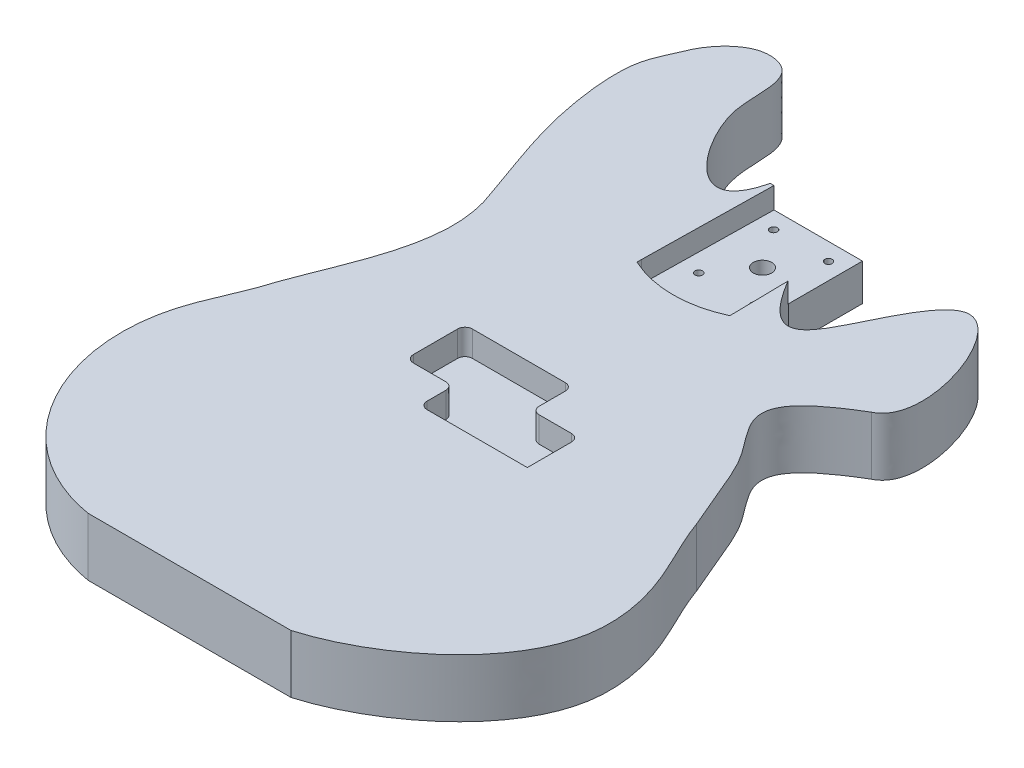
SolidWorks part; units mm, degrees
ref_plane "Front Plane" through (0, 0, 0) normal (0, 0, 1) x (1, 0, 0)
ref_plane "Top Plane" through (0, 0, 0) normal (0, 1, 0) x (1, 0, 0)
ref_plane "Right Plane" through (0, 0, 0) normal (1, 0, 0) x (0, 0, -1)
sketch "Sketch1" plane through (0, 0, 0) normal (0, 1, 0) x (1, 0, 0)
  line L0 (-31.75, 431.8) -> (31.75, 431.8)
  line L1 (-69.85, 0) -> (69.85, 0)
  line L2 (31.75, 431.8) -> (31.75, 381)
  line L3 (0, 431.8) -> (0, 0) construction
  spline S0 degree 3 poles (-69.85, 0) (-122.7459, 8.8946) (-170.3738, 68.3736) (-165.5312, 154.7593) (-147.8347, 185.8105) (-142.875, 203.2) knots 0 0 0 0 0.581043 0.783837 1 1 1 1
  spline S1 degree 3 poles (-142.875, 203.2) (-128.6398, 243.0991) (-104.4904, 285.9502) (-122.2248, 330.2) knots 0 0 0 0 1 1 1 1
  spline S2 degree 3 poles (-122.2248, 330.2) (-131.7635, 357.8566) (-146.2426, 392.3515) (-152.7726, 455.2781) (-144.5433, 471.0132) (-135.4704, 492.8612) (-120.6511, 508.7509) (-90.8297, 507.3178) (-88.3646, 481.7202) (-88.7047, 444.4419) (-43.0115, 384.6457) (-31.75, 431.8) knots 0 0 0 0 0.228271 0.373681 0.455315 0.473382 0.545352 0.564859 0.659458 0.744201 1 1 1 1
  spline S3 degree 3 poles (69.85, 0) (111.9348, 12.1111) (186.0145, 65.7497) (170.8416, 155.4983) (152.3381, 185.6263) (146.05, 203.2) knots 0 0 0 0 0.586136 0.784814 1 1 1 1
  spline S4 degree 3 poles (146.05, 203.2) (136.1599, 225.6504) (132.5896, 236.8474) (120.3836, 260.933) (109.5687, 273.3596) (96.5902, 297.0243) (109.0963, 311.9927) (139.7, 330.2) knots 0 0 0 0 0.33898 0.396393 0.554386 0.616722 1 1 1 1
  spline S5 degree 3 poles (139.7, 330.2) (166.4459, 342.892) (123.5038, 464.5308) (76.8127, 369.3895) (59.5093, 333.6668) (31.75, 381) knots 0 0 0 0 0.451982 0.679896 1 1 1 1
  point P5 (0, 412.75)
  point P7 (0, 0)
  point P10 (0, 50.8)
  point P11 (0, 101.6)
  point P12 (0, 152.4)
  point P13 (0, 177.8)
  point P15 (0, 203.2)
  point P17 (0, 254)
  point P18 (0, 279.4)
  point P19 (0, 330.2)
  point P20 (0, 406.4)
  point P21 (0, 381)
  point P22 (0, 482.6)
  point P23 (0, 508)
  point P24 (0, 457.2)
  point P25 (0, 355.6)
  point P38 (0, 422.275)
  dimension "D5" = 50.8
  dimension "D35" = 149.225
  dimension "D42" = 139.7
  dimension "D1" = 63.5
  dimension "D2" = 139.7
  dimension "D4" = 431.8
  dimension "D6" = 101.6
  dimension "D7" = 152.4
  dimension "D8" = 177.8
  dimension "D9" = 203.2
  dimension "D10" = 254
  dimension "D11" = 279.4
  dimension "D12" = 330.2
  dimension "D13" = 381
  dimension "D14" = 406.4
  dimension "D15" = 457.2
  dimension "D16" = 482.6
  dimension "D17" = 508
  dimension "D18" = 146.05
  dimension "D19" = 165.1
  dimension "D20" = 161.925
  dimension "D21" = 152.4
  dimension "D22" = 142.875
  dimension "D23" = 123.825
  dimension "D24" = 117.475
  dimension "D25" = 122.2248
  dimension "D26" = 139.7
  dimension "D27" = 146.05
  dimension "D28" = 149.225
  dimension "D29" = 139.7
  dimension "D30" = 107.95
  dimension "D31" = 88.9
  dimension "D32" = 85.725
  dimension "D33" = 6.35
  dimension "D34" = 53.975
  dimension "D36" = 174.625
  dimension "D37" = 168.275
  dimension "D38" = 157.1498
  dimension "D39" = 146.05
  dimension "D40" = 123.825
  dimension "D41" = 106.3498
  dimension "D43" = 355.6
  dimension "D44" = 422.275
  dimension "D45" = 146.05
  dimension "D46" = 114.3
  dimension "D47" = 82.55
  dimension "D48" = 66.675
extrude "Boss-Extrude1" add sketch "Sketch1" along normal blind 40.005
sketch "Sketch2" plane through (0, 40.005, 0) normal (0, 1, 0) x (1, 0, 0)
  line L0 (-29.21, 431.8) -> (31.75, 431.8)
  line L1 (31.75, 431.8) -> (-31.75, 431.8) construction
  line L2 (31.75, 381) -> (31.75, 431.8) construction
  line L3 (-29.21, 431.8) -> (-30.6832, 341.9475)
  line L4 (31.75, 431.8) -> (33.2232, 341.9475)
  line L5 (1.27, 431.8) -> (1.27, 340.7706) construction
  line L6 (-30.6832, 341.9475) -> (33.2232, 341.9475) construction
  line L7 (33.2232, 341.9475) -> (33.2232, 338.8995)
  line L8 (-30.6832, 341.9475) -> (-30.6832, 338.8995)
  line L9 (1.27, 407.1241) -> (1.27, 331.7875) construction
  arc A0 (-30.6832, 338.8995) -> (33.2232, 338.8995) centre (1.27, 407.1241) ccw
  point P13 (1.27, 341.9475)
  dimension "D5" = 7.112
  dimension "D1" = 60.96
  dimension "D2" = 89.8525
  dimension "D3" = 63.9064
  dimension "D4" = 3.048
extrude "Cut-Extrude1" cut sketch "Sketch2" against normal blind 14.605
sketch "Sketch3" plane through (0, 25.4, 0) normal (0, 1, 0) x (1, 0, 0)
  line L0 (1.27, 431.8) -> (1.27, 393.3952) construction
  line L1 (31.75, 431.8) -> (-29.21, 431.8) construction
  line L2 (31.75, 381) -> (31.75, 431.8) construction
  line L5 (33.2232, 341.9475) -> (32.6067, 379.5515) construction
  line L6 (-29.21, 431.8) -> (-30.6832, 341.9475) construction
  circle A0 centre (1.27, 393.3952) radius 6.35
  circle A1 centre (-17.526, 419.862) radius 2.54
  circle A2 centre (20.2692, 419.862) radius 2.54
  circle A3 centre (20.5972, 368.3) radius 2.54
  circle A4 centre (-17.5491, 368.3) radius 2.54
  point P0 (1.27, 399.7452)
  point P14 (-17.526, 422.402)
  point P15 (20.2692, 422.402)
  point P17 (22.8092, 419.862)
  point P19 (-14.986, 419.862)
  point P20 (23.1372, 368.3)
  point P21 (-20.0891, 368.3)
  point P22 (-17.5491, 370.84)
  point P23 (20.5972, 370.84)
  point P24 (-15.0091, 368.3)
  point P28 (18.0572, 368.3)
  point P30 (0, 0)
  point P31 (0, 0)
  point P32 (0, 0)
  dimension "D1" = 5.08
  dimension "D2" = 12.7
  dimension "D3" = 32.0548
  dimension "D4" = 9.398
  dimension "D5" = 8.9408
  dimension "D6" = 46.736
  dimension "D7" = 15.24
  dimension "D8" = 14.732
  dimension "D9" = 60.96
extrude "Cut-Extrude2" cut sketch "Sketch3" against normal through all
sketch "Sketch4" plane through (0, 40.005, 0) normal (0, 1, 0) x (1, 0, 0)
  line L0 (31.75, 431.8) -> (-29.21, 431.8) construction
  line L1 (-47.498, 242.316) -> (16.51, 242.316)
  line L2 (-52.578, 237.236) -> (-52.578, 206.756)
  line L3 (-47.498, 201.676) -> (-25.146, 201.676)
  line L4 (21.59, 237.236) -> (21.59, 219.202)
  line L5 (26.67, 214.122) -> (49.022, 214.122)
  line L6 (-20.066, 196.596) -> (-20.066, 183.642)
  line L7 (-14.986, 178.562) -> (54.102, 178.562)
  line L8 (54.102, 209.042) -> (54.102, 178.562)
  line L9 (31.75, 381) -> (31.75, 431.8) construction
  arc A0 (-20.066, 183.642) -> (-14.986, 178.562) centre (-14.986, 183.642) ccw
  arc A1 (49.022, 214.122) -> (54.102, 209.042) centre (49.022, 209.042) cw
  arc A2 (26.67, 214.122) -> (21.59, 219.202) centre (26.67, 219.202) cw
  arc A3 (-25.146, 201.676) -> (-20.066, 196.596) centre (-25.146, 196.596) cw
  arc A4 (-52.578, 206.756) -> (-47.498, 201.676) centre (-47.498, 206.756) ccw
  arc A5 (16.51, 242.316) -> (21.59, 237.236) centre (16.51, 237.236) cw
  arc A6 (-47.498, 242.316) -> (-52.578, 237.236) centre (-47.498, 237.236) ccw
  dimension "D7" = 5.08
  dimension "D1" = 35.56
  dimension "D2" = 74.168
  dimension "D3" = 63.754
  dimension "2.92" = 74.168
  dimension "D4" = 106.68
  dimension "D5" = 189.484
  dimension "D6" = 10.16
extrude "Cut-Extrude3" cut sketch "Sketch4" against normal blind 17.5514
